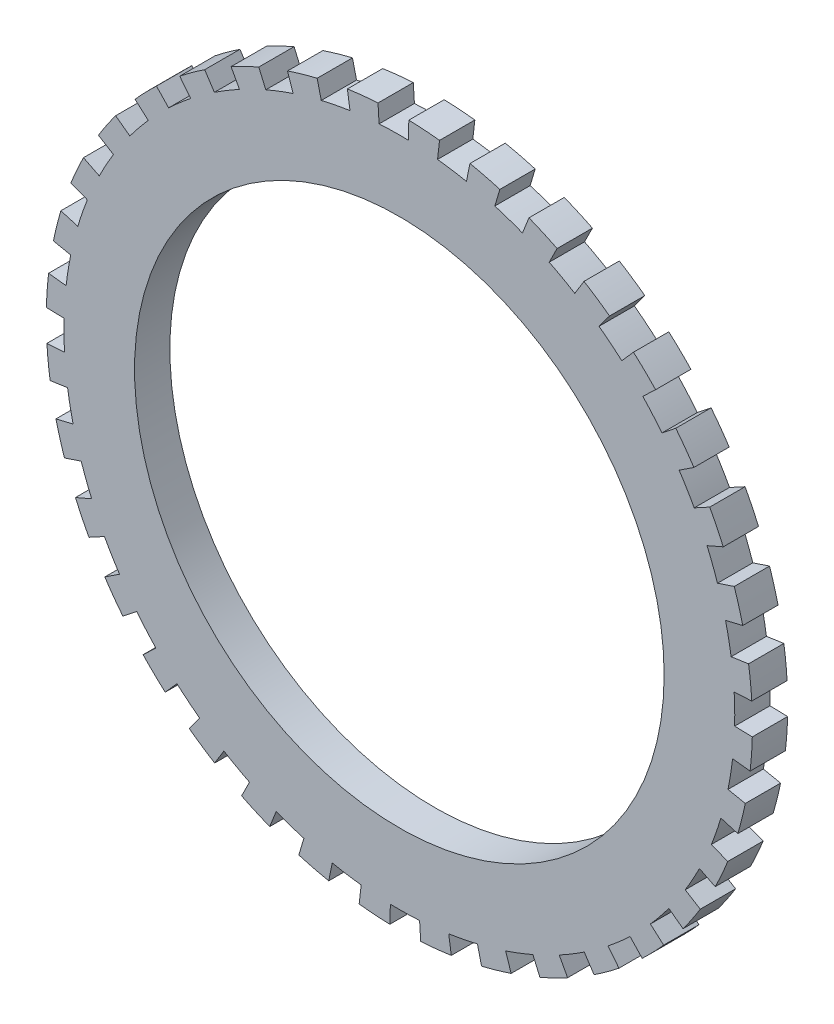
SolidWorks part; units mm, degrees
ref_plane "Front Plane" through (0, 0, 0) normal (0, 0, 1) x (1, 0, 0)
ref_plane "Top Plane" through (0, 0, 0) normal (0, 1, 0) x (1, 0, 0)
ref_plane "Right Plane" through (0, 0, 0) normal (1, 0, 0) x (0, 0, -1)
sketch "Sketch1" plane through (0, 0, 0) normal (0, 0, 1) x (1, 0, 0)
  circle A0 centre (0, 0) radius 20
  circle A1 centre (0, 0) radius 15
  dimension "D1" = 40
  dimension "D2" = 30
extrude "Boss-Extrude1" add sketch "Sketch1" along normal blind 2
sketch "Sketch2" plane through (0, 0, 2) normal (0, 0, 1) x (1, 0, 0)
  line L0 (-18.4779, -4.4236) -> (-19.4504, -4.6564)
  line L1 (-18.7931, -2.7963) -> (-19.7822, -2.9435)
  arc A0 (-19.7822, -2.9435) -> (-19.4504, -4.6564) centre (0, 0) ccw
  arc A1 (-18.7931, -2.7963) -> (-18.4779, -4.4236) centre (0, 0) ccw
  dimension "D1" = 38
  dimension "D2" = 5
extrude "Cut-Extrude1" cut sketch "Sketch2" against normal blind 2
ref_axis "Axis1" through (0, 0, 0) along (0, 0, 1)
pattern_circular "CirPattern1" count 36 over 360 about axis through (0, 0, 0) along (0, 0, 1) of "Cut-Extrude1"
scale "Scale1" scale about centroid uniform scaling yes scale factor 1.9329
scale "Scale2" scale about centroid uniform scaling yes scale factor 1.5
